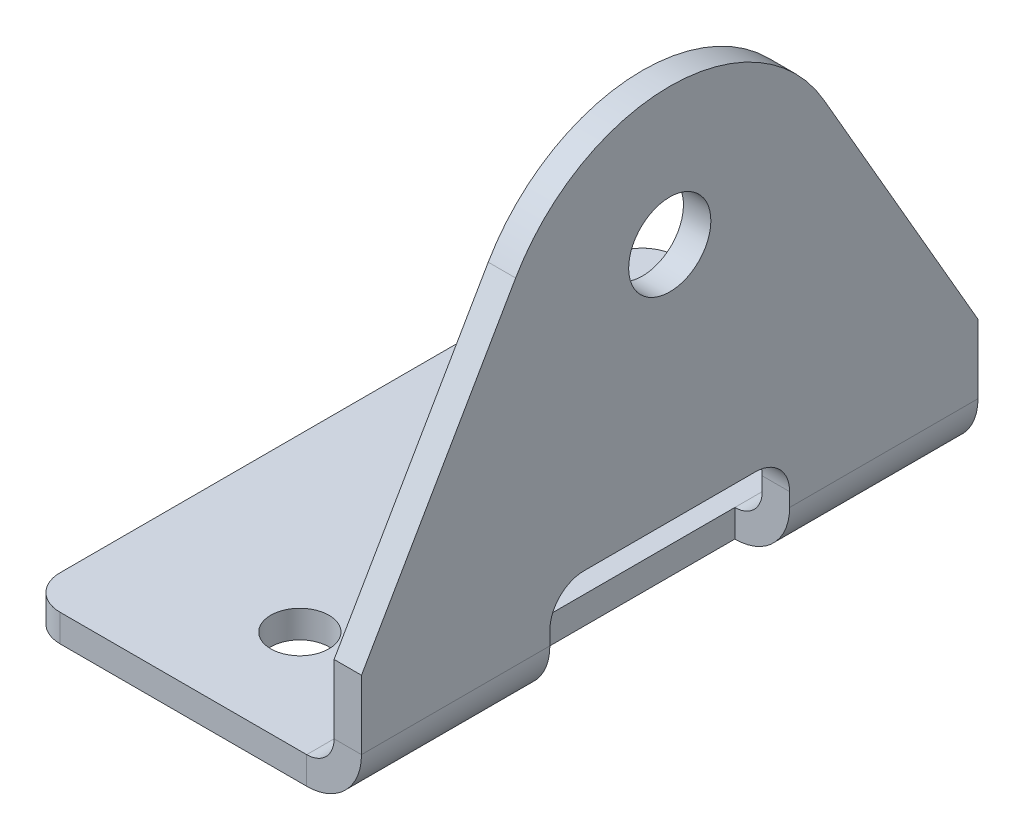
SolidWorks part; units mm, degrees
note: The reader was unsure of these and kept them because the rebuilt part matched: thickness of "Базовая кромка1", "Ребро-кромка1", "Листовой металл1", "Листовой металл2", "Листовой металл3", "Листовой металл4", "Листовой металл5"; flange length of "Ребро-кромка1".
material "1023 Листовая углеродистая сталь (SS)"
ref_plane "Спереди" through (0, 0, 0) normal (0, 0, 1) x (1, 0, 0)
ref_plane "Сверху" through (0, 0, 0) normal (0, 1, 0) x (1, 0, 0)
ref_plane "Справа" through (0, 0, 0) normal (1, 0, 0) x (0, 0, -1)
sketch "Эскиз1" plane through (0, 0, 0) normal (0, 1, 0) x (1, 0, 0)
  line L1 (20.5, -45) -> (-20.5, -45)
  line L2 (20.5, -45) -> (20.5, 45)
  line L3 (20.5, 45) -> (-20.5, 45)
  line L4 (-20.5, -45) -> (-20.5, 45)
  line L5 (20.5, -45) -> (-20.5, 45) construction
  line L6 (20.5, 45) -> (-20.5, -45) construction
  point P0 (0, 0)
  dimension "D1" = 90
  dimension "D2" = 41
base flange "Базовая кромка1" sketch "Эскиз1" thickness 4 reverse thickness direction yes parameters "D1"=4
edge flange "Ребро-кромка1" sketch "Эскиз8" flange angle 90 flange length 70 flange position bend outside bend radius 4 thickness 4 parameters "D1"=5, "D6"=10
sketch "Эскиз8" plane through (20.5, 4, 0) normal (-1, 0, 0) x (0, 0, 1)
  line L2 (-45, 0) -> (-45, 66)
  line L3 (-45, 66) -> (45, 66)
  line L4 (45, 66) -> (45, 0)
  line L13 (45, 0) -> (-45, 0) construction
  line L14 (45, 0) -> (-45, 0)
bend "EdgeBend1" bend radius 4 bend angle 90 parameters "D5"=1
sketch "Эскиз9" plane through (0, 0, 0) normal (0, -1, 0) x (1, 0, 0)
  line L0 (0, 0) -> (50000, 0) construction
  line L1 (-20.5, -45) -> (-20.5, 45) construction
  circle A0 centre (4.5, 30) radius 4.25
  circle A1 centre (4.5, -30) radius 4.25
  dimension "D3" = 8.5
  dimension "D1" = 60
  dimension "D2" = 25
extrude "Вырез-Вытянуть1" cut sketch "Эскиз9" against normal blind 10
sketch "Эскиз11" plane through (28.5, 0, 0) normal (1, 0, 0) x (0, 0, -1)
  line L0 (0, 0) -> (0, 50000) construction
  line L1 (-45, 70) -> (45, 70) construction
  circle A0 centre (0, 50) radius 6
  dimension "D1" = 12
  dimension "D2" = 20
extrude "Вырез-Вытянуть2" cut sketch "Эскиз11" against normal blind 10
sketch "Эскиз12" plane through (28.5, 0, 0) normal (1, 0, 0) x (0, 0, -1)
  line L0 (-34.25, 0) -> (-25.75, 0) construction
  line L1 (-17.5, 15) -> (17.5, 15)
  line L2 (-17.5, 15) -> (-17.5, 0)
  line L3 (-17.5, 0) -> (17.5, 0)
  line L4 (17.5, 15) -> (17.5, 0)
  line L5 (0, 36.486) -> (0, -49963.514) construction
  point P8 (0, 0)
  point P9 (19.3493, 22.598)
  point P10 (19.6954, 20)
  point P11 (-2.7629, 0)
  dimension "D1" = 15
  dimension "D2" = 35
extrude "Вырез-Вытянуть3" cut sketch "Эскиз12" against normal blind 8
chamfer "Фаска1" distance 30 angle 60 2 edges at (26.5, 70, -45) (26.5, 70, 45)
fillet "Скругление1" radius 25.9808 4 edges at (26.5, 70, -15) (24.5, 70, 0) (28.5, 70, 0) (26.5, 70, 15)
fillet "Скругление2" radius 5 4 edges at (-20.5, 2, -45) (-20.5, 2, 45) (26.5, 15, -17.5) (26.5, 15, 17.5)
sketch "Сгиб-Линии1" [suppressed] plane through (0, 0, 0) normal (0, 1, 0) x (1, 0, 0)
sketch "Граничная рамка1" [suppressed] plane through (0, 0, 0) normal (0, 1, 0) x (1, 0, 0)
sheet metal parameters "Листовой металл1" thickness 4 parameters "D1"=5, "D7"=5
flat pattern "Развертка1" [suppressed]
sketch "Сгиб-Линии2" plane through (0, 0, 0) normal (0, 1, 0) x (1, 0, 0)
sketch3d "Граничная рамка2" [suppressed]
  line L0 (-20, 30, 0) -> (-20, -30, 0) construction
  line L1 (20, 30, 0) -> (20, -30, 0) construction
  line L2 (-20, 30, 0) -> (20, 30, 0) construction
  line L3 (-20, -30, 0) -> (20, -30, 0) construction
sheet metal parameters "Листовой металл2" thickness 4 parameters "D1"=5, "D7"=5
flat pattern "Развертка1"
sketch "Сгиб-Линии2" plane through (0, 0, 0) normal (0, -1, 0) x (-1, 0, 0)
  line L0 (-25.8905, 30) -> (-25.8905, -30) construction
  line L1 (-25.8905, 30) -> (-25.8905, -30) construction
sketch3d "Граничная рамка2" [suppressed]
  line L0 (-81.781, -30, 0) -> (20, -30, 0) construction
  line L1 (-81.781, 30, 0) -> (20, 30, 0) construction
  line L2 (-81.781, -30, 0) -> (-81.781, 30, 0) construction
  line L3 (20, -30, 0) -> (20, 30, 0) construction
bend of the flat pattern "Плоское состояние-<EdgeBend1>1"
sheet metal parameters "Листовой металл3" thickness 4 parameters "D1"=5, "D7"=5
flat pattern "Развертка1"
sketch "Сгиб-Линии2" plane through (0, 0, 0) normal (0, -1, 0) x (-1, 0, 0)
  line L0 (-25.8905, 45) -> (-25.8905, -45) construction
  line L1 (-25.8905, 45) -> (-25.8905, -45) construction
sketch3d "Граничная рамка2" [suppressed]
  line L0 (-91.781, -45, 0) -> (20, -45, 0) construction
  line L1 (-91.781, 45, 0) -> (20, 45, 0) construction
  line L2 (-91.781, -45, 0) -> (-91.781, 45, 0) construction
  line L3 (20, -45, 0) -> (20, 45, 0) construction
bend of the flat pattern "Плоское состояние-<EdgeBend1>1"
sheet metal parameters "Листовой металл4" thickness 4 parameters "D1"=5, "D7"=5
flat pattern "Развертка1"
sketch "Сгиб-Линии2" plane through (0, 0, 0) normal (0, -1, 0) x (-1, 0, 0)
  line L0 (-25.2124, 45) -> (-25.2124, -45) construction
  line L1 (-25.2124, 45) -> (-25.2124, -45) construction
sketch3d "Граничная рамка2" [suppressed]
  line L0 (-91.9248, -45, 0) -> (20.5, -45, 0) construction
  line L1 (-91.9248, 45, 0) -> (20.5, 45, 0) construction
  line L2 (-91.9248, -45, 0) -> (-91.9248, 45, 0) construction
  line L3 (20.5, -45, 0) -> (20.5, 45, 0) construction
bend of the flat pattern "Плоское состояние-<EdgeBend1>1"
sheet metal parameters "Листовой металл5" thickness 4 parameters "D1"=5, "D7"=5
flat pattern "Развертка1"
sketch "Сгиб-Линии2" plane through (0, 0, 0) normal (0, -1, 0) x (-1, 0, 0)
  line L0 (-25.2124, -17.5) -> (-25.2124, -45) construction
  line L1 (-25.2124, -17.5) -> (-25.2124, -45) construction
  line L2 (-25.2124, 45) -> (-25.2124, 17.5) construction
sketch3d "Граничная рамка2" [suppressed]
  line L0 (20.5, -45, 0) -> (-91.9248, -45, 0) construction
  line L1 (20.5, 45, 0) -> (-91.9248, 45, 0) construction
  line L2 (20.5, -45, 0) -> (20.5, 45, 0) construction
  line L3 (-91.9248, -45, 0) -> (-91.9248, 45, 0) construction
bend of the flat pattern "Плоское состояние-<EdgeBend1>1"
